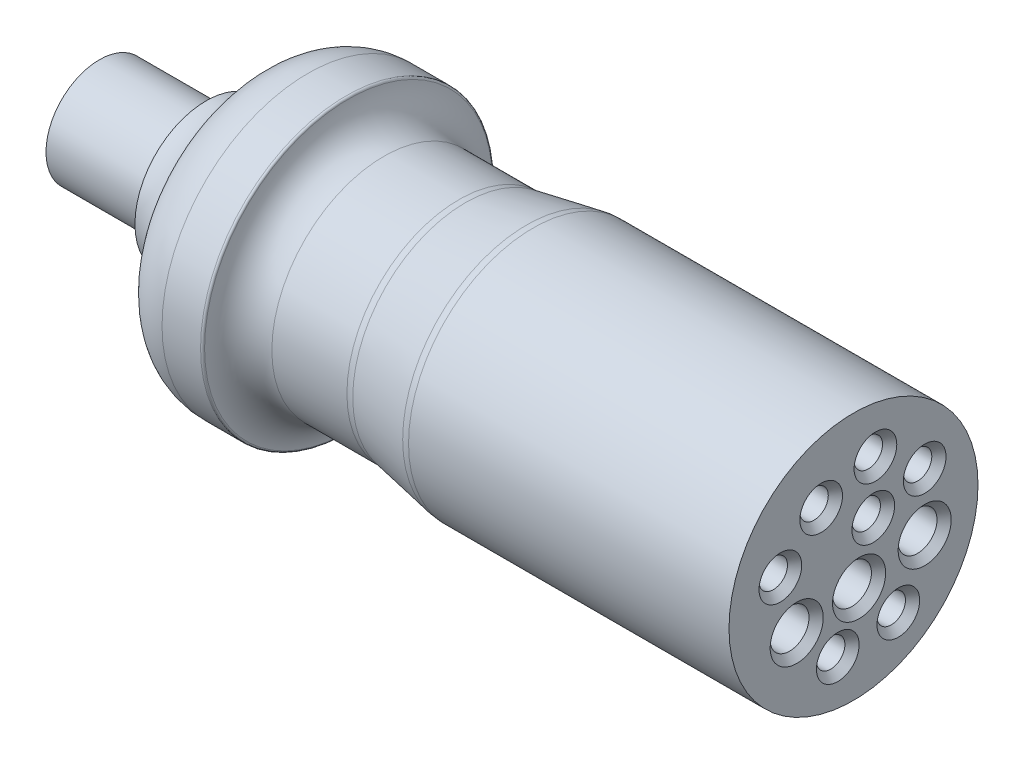
SolidWorks part; units mm, degrees
ref_plane "Front Plane" through (0, 0, 0) normal (0, 0, 1) x (1, 0, 0)
ref_plane "Top Plane" through (0, 0, 0) normal (0, 1, 0) x (1, 0, 0)
ref_plane "Right Plane" through (0, 0, 0) normal (1, 0, 0) x (0, 0, -1)
sketch "Sketch3" plane through (0, 0, 0) normal (0, 0, 1) x (1, 0, 0)
  line L0 (0, 0) -> (0, -50000) construction
  line L1 (0, 0) -> (50000, 0) construction
  line L2 (45.5, 0) -> (45.5, 17.5)
  line L3 (45.5, 17.5) -> (0, 17.5)
  line L4 (0, 17.5) -> (-9.5, 15.75)
  line L5 (-9.5, 15.75) -> (-25.5, 15.75)
  line L6 (-25.5, 15.75) -> (-25.5, 20.5)
  line L7 (-45.5, 0) -> (-45.5, 53.8042) construction
  line L8 (-25.5, 20.5) -> (-31.1909, 20.5)
  line L9 (-45.5, 10) -> (-36.3733, 10) construction
  line L10 (-45.5, 10) -> (-45.5, 0)
  line L11 (-45.5, 0) -> (45.5, 0)
  arc A0 (-45.5, 10) -> (-38.8224, 14.9) centre (-45.5, 17) ccw
  arc A1 (-38.8224, 14.9) -> (-31.1909, 20.5) centre (-31.1909, 12.5) cw
  dimension "D8" = 20
  dimension "D9" = 7
  dimension "D10" = 8
  dimension "D1" = 17.5
  dimension "D2" = 45.5
  dimension "D3" = 9.5
  dimension "D4" = 31.5
  dimension "D5" = 41
  dimension "D6" = 71
  dimension "D7" = 20
revolve "Revolve1" add sketch "Sketch3" angle 360 about L1
fillet "Fillet1" radius 5 1 edges at (-25.5, 0, 15.75)
fillet "Fillet2" radius 0.3 1 edges at (-25.5, 0, 20.5)
fillet "Fillet3" radius 5 2 edges at (0, 0, 17.5) (-9.5, 0, 15.75)
sketch "Sketch6" plane through (45.5, 0, 0) normal (1, 0, 0) x (0, 0, -1)
  line L0 (-16.3442, -6.4134) -> (3.8869, -6.4134) construction
  circle A0 centre (2.7838, 3.3454) radius 2.0006
  circle A1 centre (3.0831, 10.6474) radius 2.0006
  circle A2 centre (-4.5453, 8.2222) radius 2.0006
  circle A3 centre (-10.2777, 2.6222) radius 2.0006
  circle A4 centre (10.006, 5.7088) radius 2.0006
  circle A5 centre (-2.2083, -11.0914) radius 2.0006
  circle A6 centre (6.302, -9.9449) radius 2.0006
  circle A7 centre (10.006, -2.3606) radius 2.7332
  circle A8 centre (0.7901, -4.2126) radius 2.7332
  circle A9 centre (-7.9847, -5.2708) radius 2.7332
extrude "Cut-Extrude1" cut sketch "Sketch6" against normal blind 21
chamfer "Chamfer1" distance 1 angle 45 10 edges at (45.5, -5.2708, 5.2516) (45.5, -11.0914, 0.2077) (45.5, -9.9449, -8.3026) (45.5, -4.2126, -3.5233) (45.5, 3.3454, -4.7844) (45.5, -2.3606, -12.7391) (45.5, 5.7088, -12.0066) (45.5, 10.6474, -5.0837) (45.5, 8.2222, 2.5447) (45.5, 2.6222, 8.2771)
sketch "Sketch7" plane through (-45.5, 0, 0) normal (-1, 0, 0) x (0, 0, 1)
  circle A0 centre (0, 0) radius 7.5
  dimension "D1" = 15
extrude "Extrude-Thin1" add sketch "Sketch7" along normal blind 15 thin thin type one direction reverse wall 0.5
